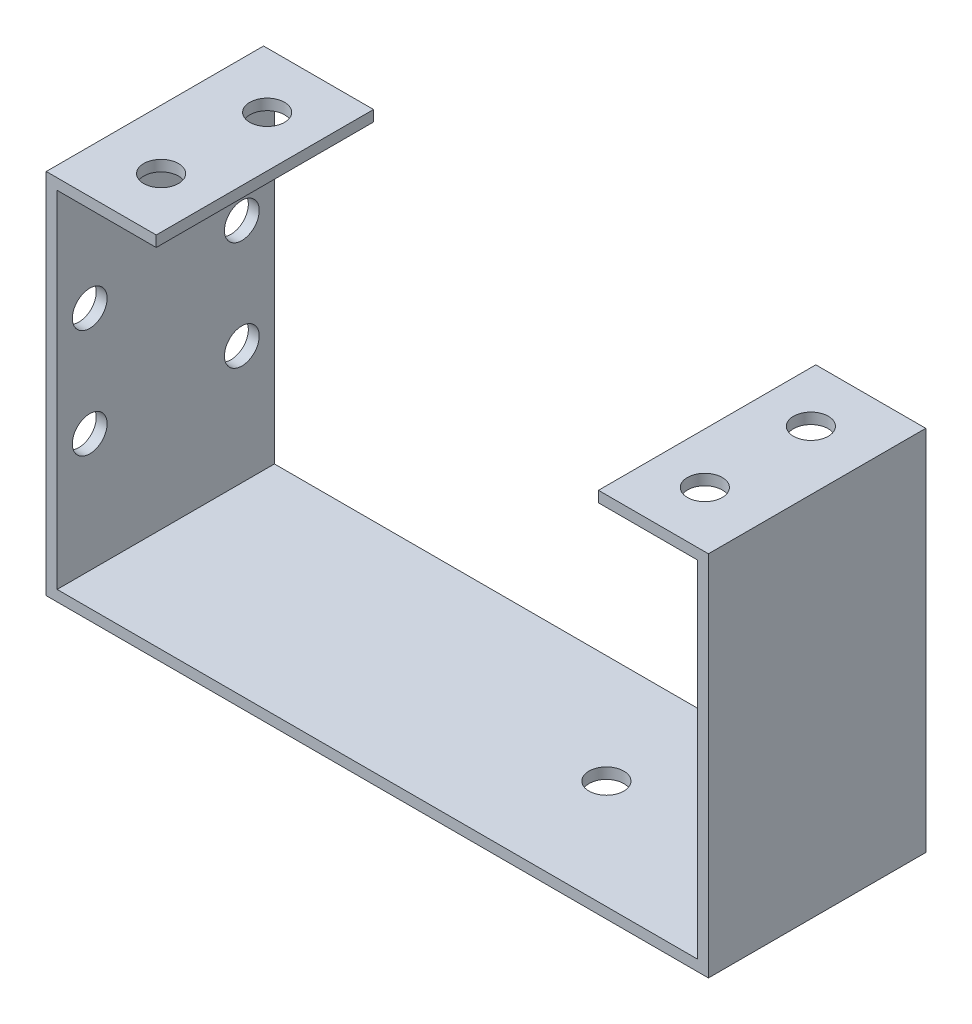
SolidWorks part; units mm, degrees
ref_plane "正面" through (0, 0, 0) normal (0, 0, 1) x (1, 0, 0)
ref_plane "平面" through (0, 0, 0) normal (0, 1, 0) x (1, 0, 0)
ref_plane "右側面" through (0, 0, 0) normal (1, 0, 0) x (0, 0, -1)
sketch "ｽｹｯﾁ2" plane through (0, 0, 0) normal (0, 1, 0) x (1, 0, 0)
  line L1 (0, 0) -> (60.94, 0)
  line L2 (0, 0) -> (0, 20)
  line L3 (0, 20) -> (60.94, 20)
  line L4 (60.94, 0) -> (60.94, 20)
extrude "ﾎﾞｽ - 押し出し1" add sketch "ｽｹｯﾁ2" along normal blind 1
sketch "ｽｹｯﾁ3" plane through (0, 1, 0) normal (0, 1, 0) x (1, 0, 0)
  line L0 (0, 0) -> (60.94, 0) construction
  line L1 (60.94, 20) -> (59.94, 20)
  line L2 (60.94, 20) -> (60.94, 0)
  line L3 (60.94, 0) -> (59.94, 0)
  line L4 (59.94, 20) -> (59.94, 0)
extrude "ﾎﾞｽ - 押し出し2" add sketch "ｽｹｯﾁ3" along normal blind 32.81
sketch "ｽｹｯﾁ4" plane through (0, 1, 0) normal (0, 1, 0) x (1, 0, 0)
  line L0 (0, 0) -> (59.94, 0) construction
  line L1 (0, 20) -> (1, 20)
  line L2 (0, 20) -> (0, 0)
  line L3 (0, 0) -> (1, 0)
  line L4 (1, 20) -> (1, 0)
extrude "ﾎﾞｽ - 押し出し3" add sketch "ｽｹｯﾁ4" along normal blind 32.81
sketch "ｽｹｯﾁ9" plane through (59.94, 0, 0) normal (-1, 0, 0) x (0, 0, 1)
  line L0 (0, 33.81) -> (0, 1) construction
  line L1 (-20, 33.81) -> (0, 33.81)
  line L2 (-20, 33.81) -> (-20, 32.81)
  line L3 (-20, 32.81) -> (0, 32.81)
  line L4 (0, 33.81) -> (0, 32.81)
extrude "ﾎﾞｽ - 押し出し8" add sketch "ｽｹｯﾁ9" along normal blind 9.12
sketch "ｽｹｯﾁ10" plane through (1, 0, 0) normal (1, 0, 0) x (0, 0, -1)
  line L0 (20, 33.81) -> (20, 1) construction
  line L1 (0, 33.81) -> (20, 33.81)
  line L2 (0, 33.81) -> (0, 32.81)
  line L3 (0, 32.81) -> (20, 32.81)
  line L4 (20, 33.81) -> (20, 32.81)
extrude "ﾎﾞｽ - 押し出し9" add sketch "ｽｹｯﾁ10" along normal blind 9.12
sketch "ｽｹｯﾁ13" plane through (0, 33.81, 0) normal (0, 1, 0) x (1, 0, 0)
  circle A0 centre (55.49, 5.12) radius 1.6
extrude "ｶｯﾄ - 押し出し2" cut sketch "ｽｹｯﾁ13" against normal blind 1
sketch "ｽｹｯﾁ14" plane through (0, 33.81, 0) normal (0, 1, 0) x (1, 0, 0)
  circle A0 centre (55.49, 14.88) radius 1.6
extrude "ｶｯﾄ - 押し出し3" cut sketch "ｽｹｯﾁ14" against normal blind 1
sketch "ｽｹｯﾁ15" plane through (0, 33.81, 0) normal (0, 1, 0) x (1, 0, 0)
  circle A0 centre (5.45, 5.12) radius 1.6
extrude "ｶｯﾄ - 押し出し4" cut sketch "ｽｹｯﾁ15" against normal blind 1
sketch "ｽｹｯﾁ16" plane through (0, 33.81, 0) normal (0, 1, 0) x (1, 0, 0)
  circle A0 centre (5.45, 14.88) radius 1.6
extrude "ｶｯﾄ - 押し出し5" cut sketch "ｽｹｯﾁ16" against normal blind 1
sketch "ｽｹｯﾁ17" plane through (0, 0, 0) normal (0, -1, 0) x (-1, 0, 0)
  circle A0 centre (-41.55, 10) radius 1.6
extrude "ｶｯﾄ - 押し出し6" cut sketch "ｽｹｯﾁ17" against normal blind 1 contours A0
sketch "ｽｹｯﾁ19" plane through (0, 0, 0) normal (-1, 0, 0) x (0, 0, 1)
  circle A0 centre (-3, 21.905) radius 1.6
  point P2 (-44.1806, 3.4289)
extrude "ｶｯﾄ - 押し出し7" cut sketch "ｽｹｯﾁ19" against normal blind 1
sketch "ｽｹｯﾁ20" plane through (0, 0, 0) normal (-1, 0, 0) x (0, 0, 1)
  circle A0 centre (-17, 21.905) radius 1.6
extrude "ｶｯﾄ - 押し出し8" cut sketch "ｽｹｯﾁ20" against normal blind 1
sketch "ｽｹｯﾁ22" plane through (0, 0, 0) normal (-1, 0, 0) x (0, 0, 1)
  circle A0 centre (-3, 11.905) radius 1.6
extrude "ｶｯﾄ - 押し出し9" cut sketch "ｽｹｯﾁ22" against normal blind 1
sketch "ｽｹｯﾁ23" plane through (0, 0, 0) normal (-1, 0, 0) x (0, 0, 1)
  circle A0 centre (-17, 11.905) radius 1.6
extrude "ｶｯﾄ - 押し出し10" cut sketch "ｽｹｯﾁ23" against normal blind 1
